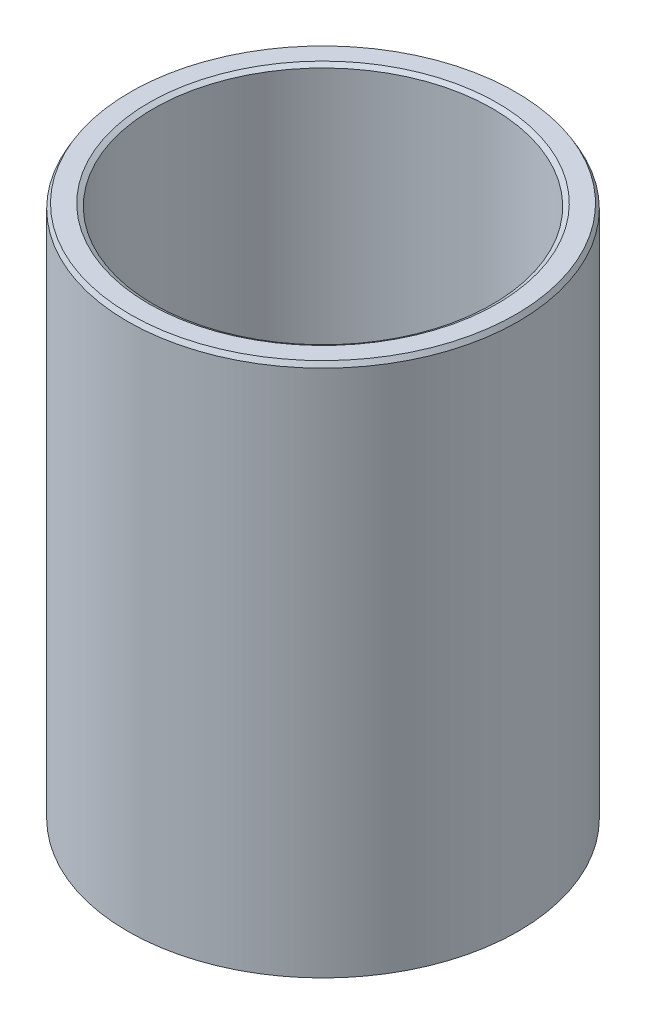
SolidWorks part; units mm, degrees
ref_plane "Front Plane" through (0, 0, 0) normal (0, 0, 1) x (1, 0, 0)
ref_plane "Top Plane" through (0, 0, 0) normal (0, 1, 0) x (1, 0, 0)
ref_plane "Right Plane" through (0, 0, 0) normal (1, 0, 0) x (0, 0, -1)
sketch "Sketch1" plane through (0, 0, 0) normal (0, 1, 0) x (1, 0, 0)
  circle A0 centre (0, 0) radius 42.5
  dimension "SLEEVE_OD" = 85
extrude "Boss-Extrude1" add sketch "Sketch1" along normal blind 116.4611
sketch "Sketch2" plane through (0, 0, 0) normal (0, 1, 0) x (1, 0, 0)
  circle A0 centre (0, 0) radius 36.8675
  dimension "BORE_D" = 73.7351
extrude "Cut-Extrude1" cut sketch "Sketch2" along normal through all
chamfer "Chamfer1" distance 1.0133 angle 30 4 edges at (0, 116.4611, 36.8675) (0, 0, 36.8675) (0, 0, 42.5) (0, 116.4611, 42.5) first distance on face at (0, 116.4611, 36.8675) first distance on face at (0, 0, 36.8675) first distance on face at (0, 116.4611, 42.5)
